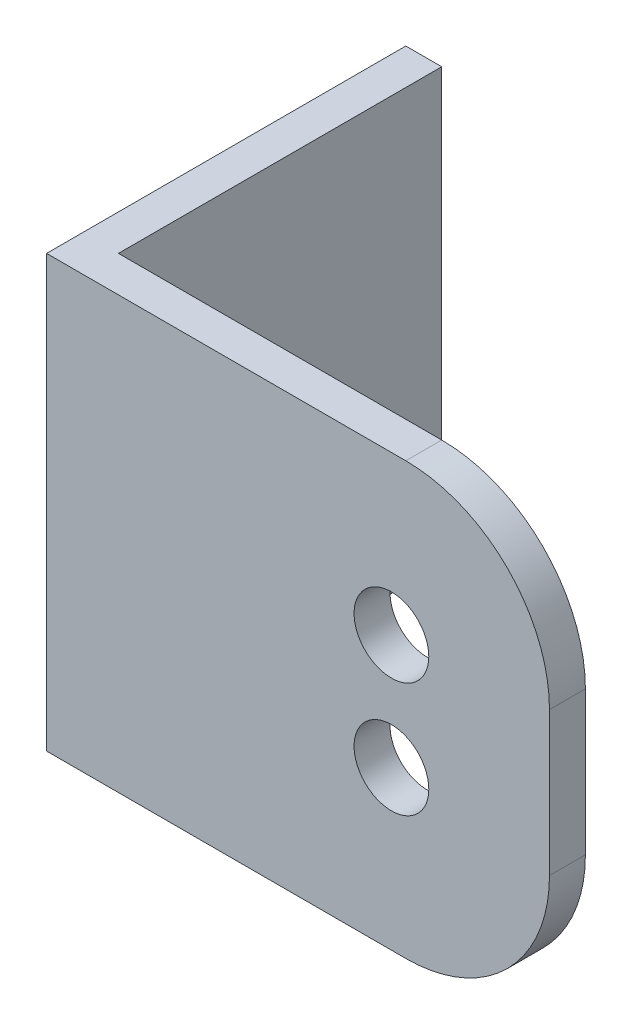
SolidWorks part; units mm, degrees
material "AISI 4130 Steel, annealed at 865C"
ref_plane "Front Plane" through (0, 0, 0) normal (0, 0, 1) x (1, 0, 0)
ref_plane "Top Plane" through (0, 0, 0) normal (0, 1, 0) x (1, 0, 0)
ref_plane "Right Plane" through (0, 0, 0) normal (1, 0, 0) x (0, 0, -1)
sketch "Sketch1" plane through (0, 0, 0) normal (0, 0, 1) x (1, 0, 0)
  line L0 (0, -374.8954) -> (0, 18369.8741) construction
  line L6 (0, 19.05) -> (44.45, 19.05)
  line L7 (0, 19.05) -> (0, -19.05)
  line L8 (0, -19.05) -> (44.45, -19.05)
  line L9 (44.45, 19.05) -> (44.45, -19.05)
  line L10 (22.225, -19.05) -> (22.225, 19.05) construction
  line L11 (0, 0) -> (44.45, 0) construction
  point P291 (22.225, 0)
  dimension "D1" = 44.45
  dimension "D2" = 38.1
extrude "Boss-Extrude1" add sketch "Sketch1" along normal blind 3.175
sketch "Sketch2" plane through (0, 0, 3.175) normal (0, 0, 1) x (1, 0, 0)
  line L0 (30.48, 5.08) -> (30.48, -5.08) construction
  line L1 (0, 0) -> (44.45, 0) construction
  line L2 (0, 19.05) -> (0, -19.05) construction
  line L3 (44.45, -19.05) -> (44.45, 19.05) construction
  circle A0 centre (30.48, 5.08) radius 3.302
  circle A1 centre (30.48, -5.08) radius 3.302
  point P4 (30.48, 0)
  dimension "D1" = 6.604
  dimension "D2" = 30.48
  dimension "D3" = 10.16
extrude "Cut-Extrude1" cut sketch "Sketch2" against normal through all both and the other way through all
sketch "Sketch3" plane through (0, 0, 0) normal (0, 0, -1) x (-1, 0, 0)
  line L0 (0, -19.05) -> (-44.45, -19.05) construction
  line L1 (0, 19.05) -> (-3.175, 19.05)
  line L2 (0, 19.05) -> (0, -19.05)
  line L3 (0, -19.05) -> (-3.175, -19.05)
  line L4 (-3.175, 19.05) -> (-3.175, -19.05)
  line L5 (-1.5875, -19.05) -> (-1.5875, 19.05) construction
  line L6 (0, 0) -> (-3.175, 0) construction
  point P148 (-1.5875, 0)
  dimension "D1" = 3.175
extrude "Boss-Extrude2" add sketch "Sketch3" along normal blind 28.575
fillet "Fillet1" radius 12.7 2 edges at (44.45, -19.05, 1.5875) (44.45, 19.05, 1.5875)
